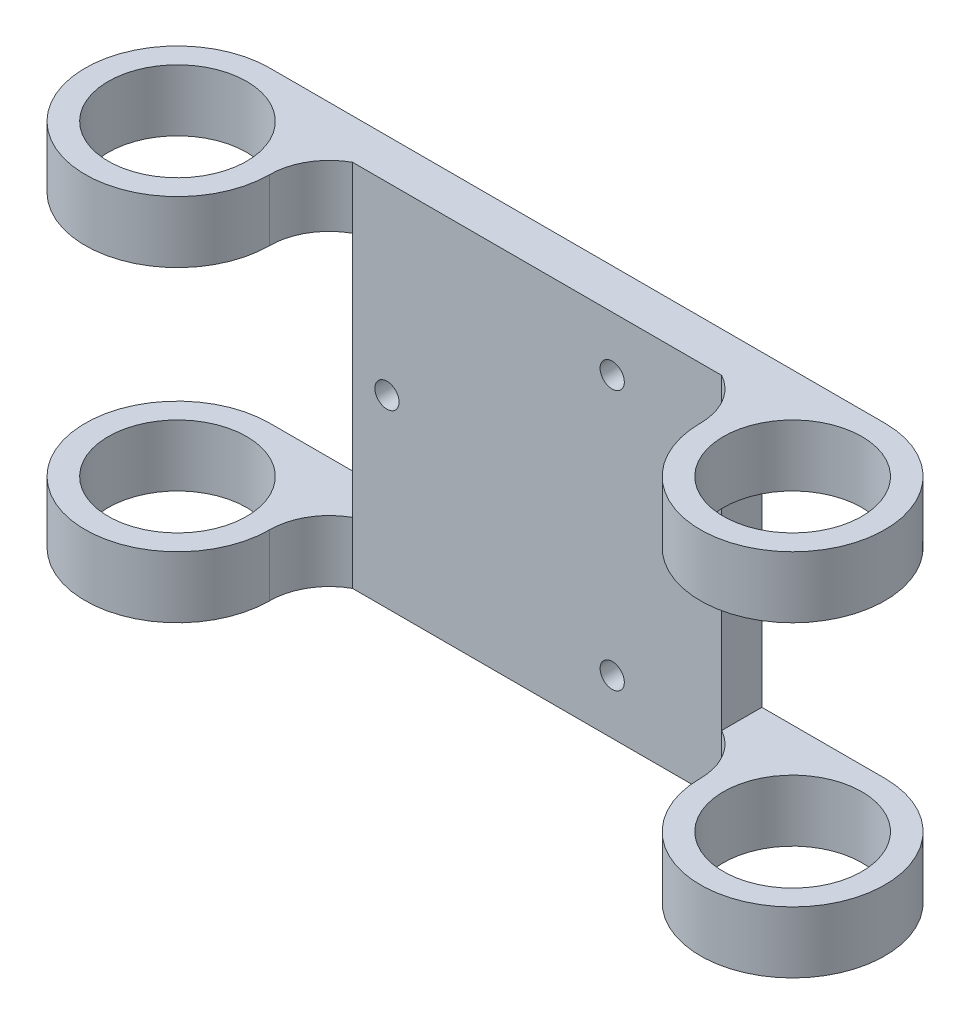
SolidWorks part; units mm, degrees
ref_plane "Front Plane" through (0, 0, 0) normal (0, 0, 1) x (1, 0, 0)
ref_plane "Top Plane" through (0, 0, 0) normal (0, 1, 0) x (1, 0, 0)
ref_plane "Right Plane" through (0, 0, 0) normal (1, 0, 0) x (0, 0, -1)
sketch "Sketch1" plane through (0, 0, 0) normal (0, 1, 0) x (1, 0, 0)
  line L0 (63.5, 0) -> (-63.5, 0)
  line L1 (-63.5, 0) -> (-63.5, -38.1) construction
  line L2 (-63.5, -38.1) -> (63.5, -38.1) construction
  line L3 (63.5, -38.1) -> (63.5, 0) construction
  line L4 (0, 0) -> (0, -38.1) construction
  line L6 (-77.7875, -19.05) -> (77.7875, -19.05) construction
  line L7 (38.1, -8.3) -> (-38.1, -8.3)
  arc A0 (-63.5, 0) -> (-44.45, -19.05) centre (-63.5, -19.05) ccw
  arc A1 (63.5, 0) -> (44.45, -19.05) centre (63.5, -19.05) cw
  circle A4 centre (-63.5, -19.05) radius 14.2875
  circle A5 centre (63.5, -19.05) radius 14.2875
  arc A8 (-44.45, -19.05) -> (-38.1, -8.3) centre (-32.1756, -19.05) cw
  arc A9 (44.45, -19.05) -> (38.1, -8.3) centre (32.1756, -19.05) ccw
  point P4 (0, 0)
  point P12 (0, -8.3)
  point P26 (0, -8.3)
  dimension "D4" = 28.575
  dimension "D1" = 38.1
  dimension "D2" = 127
  dimension "D3" = 76.2
  dimension "D5" = 8.3
extrude "Boss-Extrude1" add sketch "Sketch1" along normal blind 76.2
sketch "Sketch2" plane through (0, 0, 0) normal (0, 0, -1) x (-1, 0, 0)
  line L0 (0, 0) -> (0, 76.2) construction
  line L1 (-63.5, 76.2) -> (63.5, 76.2) construction
  line L2 (38.1, 38.1) -> (-38.1, 38.1) construction
  line L3 (-38.1, 12.7) -> (-38.1, 63.5)
  line L4 (-38.1, 63.5) -> (-38.1, 12.7)
  line L5 (-38.1, 63.5) -> (-168.0908, 63.5)
  line L6 (-38.1, 12.7) -> (-168.0908, 12.7)
  line L7 (-168.0908, 63.5) -> (-168.0908, 12.7)
  line L8 (38.1, 12.7) -> (38.1, 63.5)
  line L9 (38.1, 63.5) -> (38.1, 12.7)
  line L10 (38.1, 63.5) -> (132.1995, 63.5)
  line L11 (38.1, 12.7) -> (132.1995, 12.7)
  line L12 (132.1995, 63.5) -> (132.1995, 12.7)
  line L14 (31.0002, 38.1) -> (-15.5001, 64.947) construction
  line L15 (-15.5001, 64.947) -> (-15.5001, 11.253) construction
  line L16 (-15.5001, 11.253) -> (31.0002, 38.1) construction
  circle A0 centre (0, 38.1) radius 15.5001 construction
  circle A1 centre (-15.5001, 64.947) radius 2.5
  circle A2 centre (31.0002, 38.1) radius 2.5
  circle A3 centre (-15.5001, 11.253) radius 2.5
  point P8 (0, 38.1)
  point P9 (0, 38.1)
  point P12 (-38.1, 38.1)
  point P17 (38.1, 38.1)
  line M10 (63.5, 0) -> (63.5, 76.2)
  line M12 (-63.5, 76.2) -> (-63.5, 0)
  dimension "D4" = 5
  dimension "D1" = 50.8
  dimension "D2" = 76.2
  dimension "D3" = 53.694
extrude "Cut-Extrude1" cut sketch "Sketch2" against normal through all both and the other way through all contours L6 L3 L5 M12 | L5 L7 L6 M12 | L8 L11 L10 M10 | L12 L10 L11 M10 | A1 | A3 | A2 region at (50.8, 38.1, 0) region at (115.7954, 38.1, 0) region at (-50.8, 38.1, 0) region at (-97.8498, 38.1, 0) region at (15.5001, 64.947, 0) region at (-31.0002, 38.1, 0) region at (15.5001, 11.253, 0)
